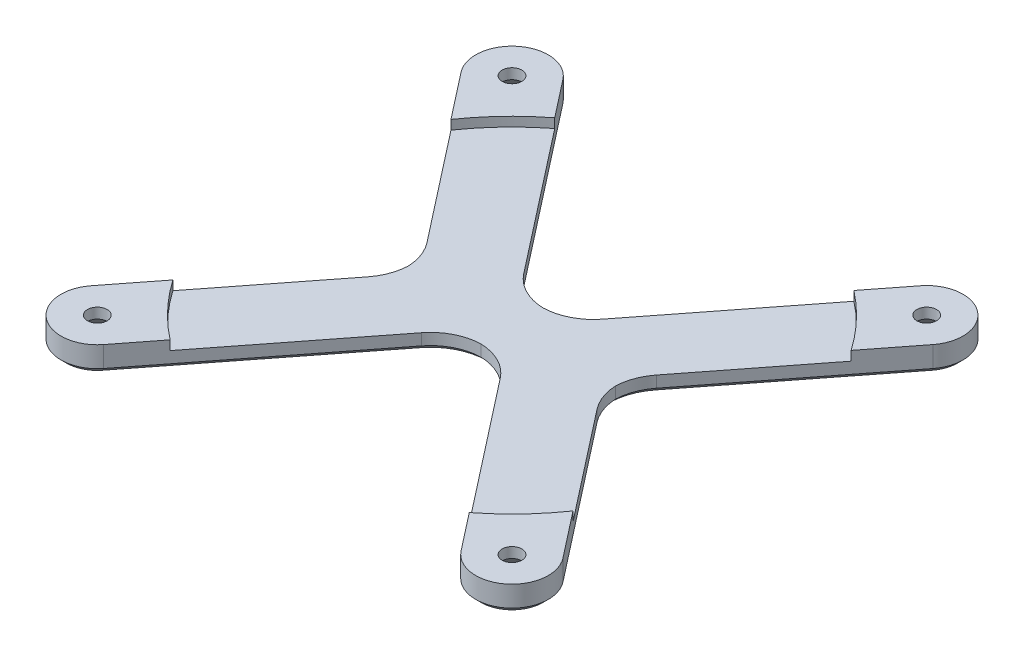
SolidWorks part; units mm, degrees
ref_plane "Спереди" through (0, 0, 0) normal (0, 0, 1) x (1, 0, 0)
ref_plane "Сверху" through (0, 0, 0) normal (0, 1, 0) x (1, 0, 0)
ref_plane "Справа" through (0, 0, 0) normal (1, 0, 0) x (0, 0, -1)
sketch "Эскиз1" plane through (0, 0, 0) normal (0, 1, 0) x (1, 0, 0)
  line L0 (0, 48.9017) -> (0, 0) construction
  line L1 (-51.9075, 0) -> (51.9075, 0) construction
  line L2 (-4.5818, 6) -> (4.5818, 6)
  line L3 (4.5818, 6) -> (34.4819, 44.3071)
  line L4 (45.5181, 35.6929) -> (20, 3)
  line L5 (20, 3) -> (20, -3)
  line L6 (45.5181, -35.6929) -> (20, -3)
  line L7 (4.5818, -6) -> (34.4819, -44.3071)
  line L8 (-4.5818, -6) -> (4.5818, -6)
  line L9 (-4.5818, -6) -> (-34.4819, -44.3071)
  line L10 (-45.5181, -35.6929) -> (-20, -3)
  line L11 (-20, 3) -> (-20, -3)
  line L12 (-45.5181, 35.6929) -> (-20, 3)
  line L13 (-4.5818, 6) -> (-34.4819, 44.3071)
  line L14 (31.7722, 46.4221) -> (40, 40) construction
  line L15 (40, 40) -> (51.8708, 30.7344) construction
  line L16 (-40, 40) -> (-29.2614, 44.7998) construction
  line L17 (-29.2614, 44.7998) -> (-51.9075, 34.6778) construction
  arc A0 (34.4819, 44.3071) -> (45.5181, 35.6929) centre (40, 40) cw
  circle A1 centre (40, 40) radius 1.9
  circle A2 centre (40, -40) radius 1.9
  arc A3 (34.4819, -44.3071) -> (45.5181, -35.6929) centre (40, -40) ccw
  arc A4 (-34.4819, -44.3071) -> (-45.5181, -35.6929) centre (-40, -40) cw
  circle A5 centre (-40, -40) radius 1.9
  circle A6 centre (-40, 40) radius 1.9
  arc A7 (-34.4819, 44.3071) -> (-45.5181, 35.6929) centre (-40, 40) ccw
  point P3 (-20, 0)
  point P13 (20, 0)
  point P29 (0, -6)
  point P32 (0, 6)
  point P36 (18.1949, 6)
  dimension "D8" = 3.8
  dimension "D1" = 40
  dimension "D2" = 40
  dimension "D3" = 14
  dimension "D4" = 6
  dimension "D5" = 6
  dimension "D6" = 20
  dimension "D7" = 9.1636
extrude "Бобышка-Вытянуть1" add sketch "Эскиз1" along normal blind 5
sketch "Эскиз2" plane through (0, 5, 0) normal (0, 1, 0) x (1, 0, 0)
  circle A0 centre (0, 0) radius 47
  dimension "D1" = 94
extrude "Вырез-Вытянуть1" cut sketch "Эскиз2" against normal blind 1.8
fillet "Скругление1" radius 10 8 edges at (20, 1.6, 3) (20, 1.6, -3) (-20, 1.6, 3) (-20, 1.6, -3) (-4.5818, 1.6, 6) (4.5818, 1.6, 6) (-4.5818, 1.6, -6) (4.5818, 1.6, -6)
chamfer "Фаска1" distance 3 angle 45 4 edges at (40, 0, 38.1) (-40, 0, 41.9) (40, 0, -38.1) (-40, 0, -41.9)
chamfer "Фаска2" distance 1 angle 45 20 edges at (-44.3071, 0, -45.5181) (44.3071, 0, -45.5181) (44.3071, 0, 45.5181) (-44.3071, 0, 45.5181) (-33.8176, 0, -20.7026) (-33.8176, 0, 20.7026) (-20.6181, 0, -3.0204) (-20.6181, 0, 3.0204) (33.8176, 0, 20.7026) (33.8176, 0, -20.7026) (20.6181, 0, 3.0204) (20.6181, 0, -3.0204) (21.0332, 0, -27.0771) (-21.0332, 0, -27.0771) (4.221, 0, -7.0795) (-4.221, 0, -7.0795) (-21.0332, 0, 27.0771) (21.0332, 0, 27.0771) (-4.221, 0, 7.0795) (4.221, 0, 7.0795)
